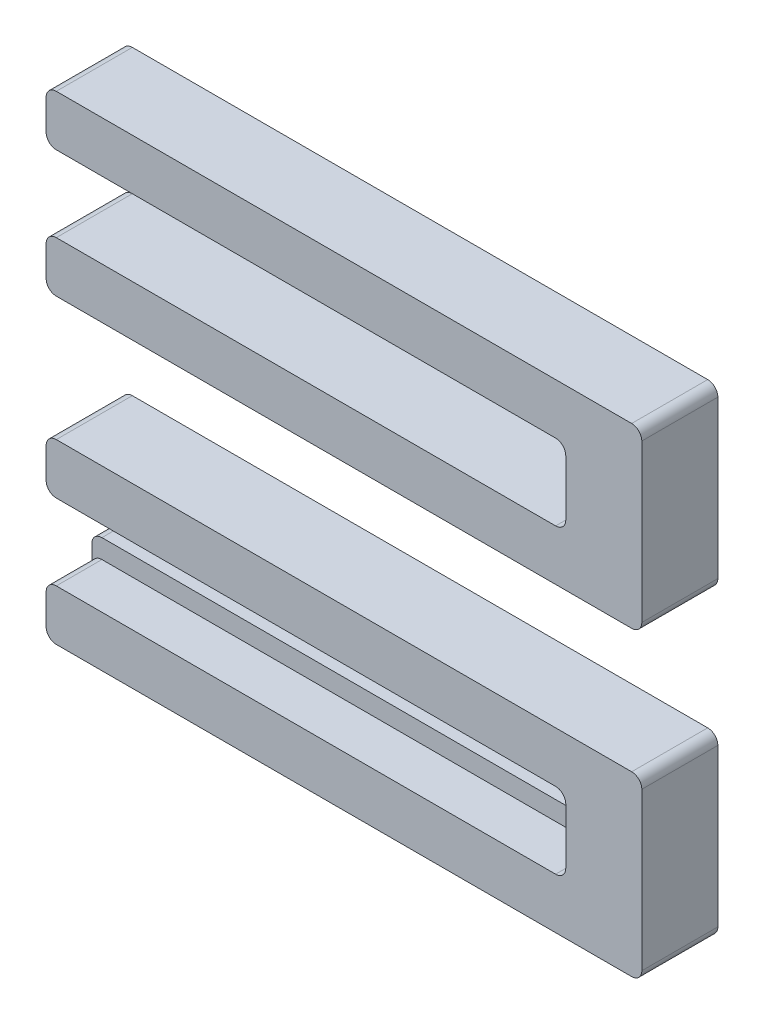
SolidWorks part; units mm, degrees
ref_plane "Front Plane" through (0, 0, 0) normal (0, 0, 1) x (1, 0, 0)
ref_plane "Top Plane" through (0, 0, 0) normal (0, 1, 0) x (1, 0, 0)
ref_plane "Right Plane" through (0, 0, 0) normal (1, 0, 0) x (0, 0, -1)
sketch "Sketch2" plane through (0, 0, 0) normal (0, 0, 1) x (1, 0, 0)
  line L0 (-2.7742, -2.4497) -> (31.3823, -2.4497) construction
  line L1 (0, 0) -> (23.5, 0)
  line L2 (0, 0) -> (0, 7)
  line L3 (0, 7) -> (23.5, 7)
  line L4 (23.5, 0) -> (23.5, 7)
  line L5 (0, 5) -> (20.5, 5)
  line L6 (0, 5) -> (0, 2)
  line L7 (0, 2) -> (20.5, 2)
  line L8 (20.5, 5) -> (20.5, 2)
  line L9 (0, 5) -> (20.5, 5)
  line L10 (0, 5) -> (0, 4.25)
  line L11 (0, 4.25) -> (20.5, 4.25)
  line L12 (20.5, 5) -> (20.5, 4.25)
  line L13 (20.5, -9.8995) -> (20.5, -9.1495)
  line L14 (0, -9.1495) -> (20.5, -9.1495)
  line L15 (0, -9.8995) -> (0, -9.1495)
  line L16 (0, -9.8995) -> (20.5, -9.8995)
  line L17 (20.5, -9.8995) -> (20.5, -6.8995)
  line L18 (0, -6.8995) -> (20.5, -6.8995)
  line L19 (0, -9.8995) -> (0, -6.8995)
  line L20 (0, -9.8995) -> (20.5, -9.8995)
  line L21 (23.5, -4.8995) -> (23.5, -11.8995)
  line L22 (0, -11.8995) -> (23.5, -11.8995)
  line L23 (0, -4.8995) -> (0, -11.8995)
  line L24 (0, -4.8995) -> (23.5, -4.8995)
  dimension "D1" = 7
  dimension "D2" = 3
  dimension "D3" = 2
  dimension "D4" = 3
  dimension "D5" = 20.5
  dimension "D6" = 2.25
extrude "Boss-Extrude1" add sketch "Sketch2" along normal blind 3 contours L5 L8 L7 L2 L1 L4 L3 | L24 L23 L18 L17 L13 L16 L22 L21 region at (0.2452, 1, 0) region at (20.7452, -9.5245, 0)
extrude "Boss-Extrude3" add sketch "Sketch2<4>" along normal blind 1.2 contours L15 L16 L13 L14 | L6 L11 L8 L5 region at (10.25, 4.625, 0) region at (10.25, -9.5245, 0)
sketch "Sketch2<4>" plane through (0, 0, 0) normal (0, 0, 1) x (1, 0, 0) same geometry as "Sketch2"
fillet "Fillet2" radius 0.4 10 edges at (0, 5, 2.1) (20.5, 2, 1.5) (20.5, 4.25, 0.6) (20.5, 5, 2.1) (23.5, 7, 1.5) (23.5, 0, 1.5) (0, 0, 1.5) (0, 2, 1.5) (0, 4.25, 0.6) (0, 7, 1.5)
fillet "Fillet3" radius 0.4 10 edges at (23.5, -11.8995, 1.5) (23.5, -4.8995, 1.5) (20.5, -6.8995, 1.5) (20.5, -9.8995, 2.1) (20.5, -9.1495, 0.6) (0, -11.8995, 1.5) (0, -9.8995, 2.1) (0, -9.1495, 0.6) (0, -4.8995, 1.5) (0, -6.8995, 1.5)
